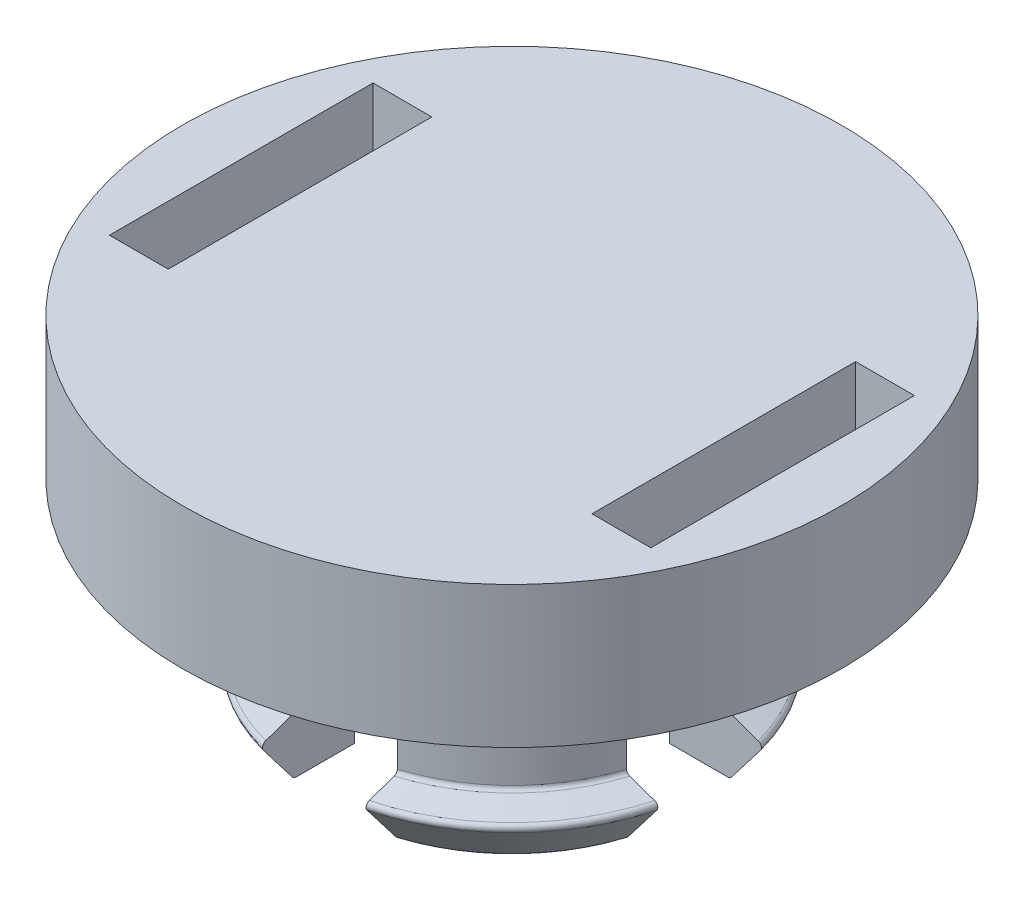
SolidWorks part; units mm, degrees
ref_plane "Front Plane" through (0, 0, 0) normal (0, 0, 1) x (1, 0, 0)
ref_plane "Top Plane" through (0, 0, 0) normal (0, 1, 0) x (1, 0, 0)
ref_plane "Right Plane" through (0, 0, 0) normal (1, 0, 0) x (0, 0, -1)
sketch "Szkic1" plane through (0, 0, 0) normal (0, 1, 0) x (1, 0, 0)
  circle A0 centre (0, 0) radius 7
  dimension "D1" = 14
extrude "Dodanie-wyciągnięcie1" add sketch "Szkic1" along normal blind 3
ref_point "Punkt1"
ref_plane "Płaszczyzna1" through (0, 0, 0) normal (0, -1, 0) x (-1, 0, 0)
sketch "Szkic2" plane through (0, 0, 0) normal (0, -1, 0) x (-1, 0, 0)
  circle A0 centre (0, 0) radius 3.7
  dimension "D1" = 7.4
extrude "Dodanie-wyciągnięcie2" add sketch "Szkic2" along normal blind 4.3
ref_axis "Oś1" through (0, -4.3, 0) along (0, 1, 0)
sketch "Szkic3" plane through (0, 0, 0) normal (1, 0, 0) x (0, 0, -1)
  line L1 (3.7, -4.3) -> (4.4, -3.3548)
  line L2 (4.4, -3.3548) -> (3.7, -3.1)
  line L4 (3.7, -3.1) -> (3.7, -4.3)
  line L5 (0, -4.3) -> (0, 0) construction
  line L7 (-7.7, 0) -> (7.7, 0) construction
  dimension "D1" = 3.7
  dimension "D2" = 1.2
  dimension "D3" = 70
  dimension "D4" = 4.3
  dimension "D5" = 4.4
revolve "Obrót1" add sketch "Szkic3" angle 360 about axis through (0, -4.3, 0) along (0, 1, 0)
fillet "Zaokrąglenie1" radius 0.1 3 edges at (0, -3.3548, -4.4) (0, -3.1, -3.7) (0, -4.3, -3.7)
ref_plane "Płaszczyzna2" through (0, -4.3, 0) normal (0, -1, 0) x (-1, 0, 0)
sketch "Szkic5" plane through (0, -4.3, 0) normal (0, -1, 0) x (-1, 0, 0)
  line L0 (-7.9807, -1.1) -> (-1.1, -1.1)
  line L1 (7.9807, 1.1) -> (1.1, 1.1)
  line L2 (-1.1, -7.9807) -> (-1.1, -1.1)
  line L3 (1.1, 7.9807) -> (1.1, 1.1)
  line L4 (-1.1, 1.1) -> (-1.1, 7.9807)
  line L5 (1.1, -1.1) -> (7.9807, -1.1)
  line L6 (1.1, -1.1) -> (1.1, -7.9807)
  line L7 (-1.1, 1.1) -> (-7.9807, 1.1)
  line L8 (-1.1, -1.1) -> (1.1, 1.1) construction
  arc A0 (-7.9807, 1.1) -> (-7.9807, -1.1) centre (0, 0) ccw
  arc A1 (-1.1, -7.9807) -> (1.1, -7.9807) centre (0, 0) ccw
  arc A2 (7.9807, -1.1) -> (7.9807, 1.1) centre (0, 0) ccw
  arc A3 (1.1, 7.9807) -> (-1.1, 7.9807) centre (0, 0) ccw
  circle A4 centre (0, 0) radius 2.5
  point P1 (0, 0)
  dimension "D3" = 5
  dimension "D1" = 2.2
  dimension "D2" = 2.2
extrude "Wytnij-wyciągnięcie1" cut sketch "Szkic5" against normal up to surface (4.3 mm away) contours L4 A4 L7 | L8 L2 A4 L6 L5 L1 | L0 L8 L3 A4 L4 L7 | L1 A4 L3 | A4 L5 A2 L1 | A4 L3 A3 L4 | A4 L7 A0 L0 | A4 L2 A1 L6 | L6 A4 L5 | L0 A4 L2 region at (5.2235, -4.3, 0) region at (0.729, -4.3, -0.729) region at (1.5234, -4.3, 1.5234) region at (-0.729, -4.3, 0.729) region at (1.5234, -4.3, -1.5234) region at (0, -4.3, 5.2235) region at (-1.5234, -4.3, -1.5234) region at (0, -4.3, -5.2235) region at (-1.5234, -4.3, 1.5234) region at (-5.2235, -4.3, 0) up to face at (0, 0, -3.7)
ref_plane "płaszczyzna dolna" through (0, 3, 0) normal (0, 1, 0) x (1, 0, 0)
sketch "Szkic8" plane through (0, 3, 0) normal (0, 1, 0) x (1, 0, 0)
  line L0 (4.5, -2.8) -> (-4.5, 2.8) construction
  line L1 (5.75, -2.8) -> (4.5, -2.8)
  line L2 (5.75, -2.8) -> (5.75, 2.8)
  line L3 (5.75, 2.8) -> (4.5, 2.8)
  line L4 (4.5, -2.8) -> (4.5, 2.8)
  line L5 (-4.5, -2.8) -> (-5.75, -2.8)
  line L6 (-4.5, -2.8) -> (-4.5, 2.8)
  line L7 (-4.5, 2.8) -> (-5.75, 2.8)
  line L8 (-5.75, -2.8) -> (-5.75, 2.8)
  point P8 (0, 0)
  dimension "D1" = 5.6
  dimension "D2" = 1.25
  dimension "D3" = 9
extrude "Wytnij-wyciągnięcie2" cut sketch "Szkic8" against normal blind 2.3
sketch "Szkic10" plane through (5.75, 0, 0) normal (-1, 0, 0) x (0, 0, 1)
  line L0 (-2.8, 1.2) -> (-2.8, 0.7)
  line L1 (-2.8, 0.7) -> (-2.8, 3) construction
  line L2 (-2.8, 0.7) -> (0, 0.7)
  line L3 (2.8, 0.7) -> (-2.8, 0.7) construction
  line L4 (0, 0.7) -> (2.8, 0.7)
  line L5 (2.8, 0.7) -> (2.8, 1.2)
  line L7 (2.8, 1.2) -> (0, 0.7)
  line L8 (-2.8, 1.2) -> (0, 0.7)
  line L9 (2.8, 0.7) -> (2.8, 3) construction
  line M6 (-2.8, 3) -> (-2.8, 0.7)
  line M7 (-2.8, 0.7) -> (2.8, 0.7)
  line M8 (2.8, 0.7) -> (2.8, 3)
  dimension "D1" = 0.5
extrude "Dodanie-wyciągnięcie3" add sketch "Szkic10" along normal blind 12 contours L8 M6 M7 | L7 M8 M7 region at (5.75, 0.8667, -1.8667) region at (5.75, 0.8667, 1.8667)
